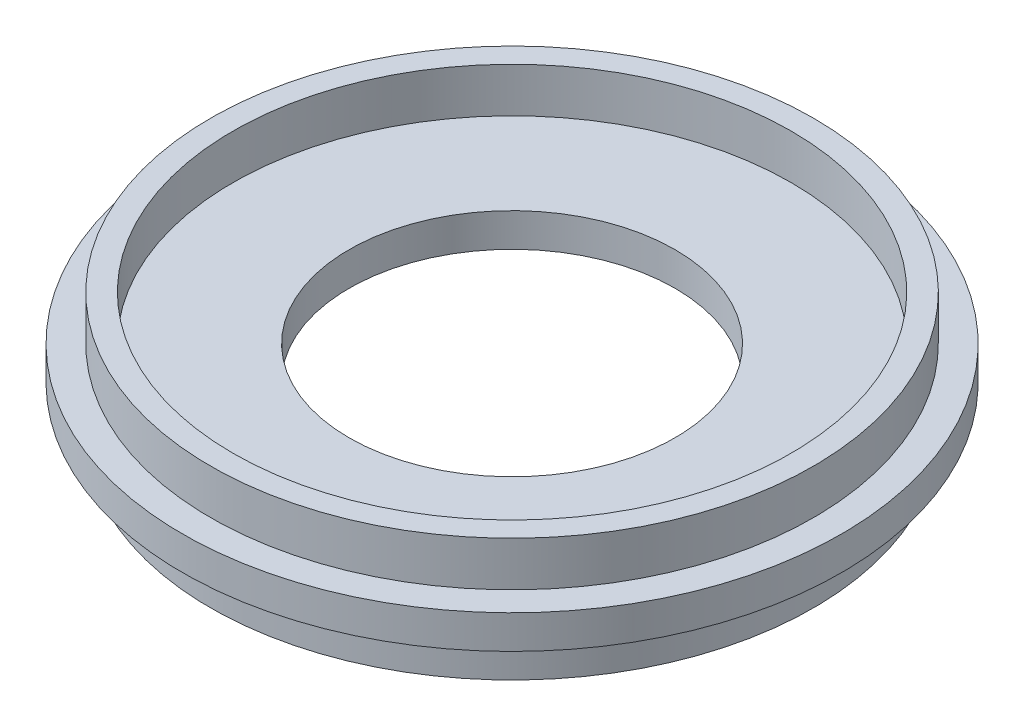
SolidWorks part; units mm, degrees
material "6061-T6 (SS)"
ref_plane "Front Plane" through (0, 0, 0) normal (0, 0, 1) x (1, 0, 0)
ref_plane "Top Plane" through (0, 0, 0) normal (0, 1, 0) x (1, 0, 0)
ref_plane "Right Plane" through (0, 0, 0) normal (1, 0, 0) x (0, 0, -1)
sketch "Sketch1" plane through (0, 0, 0) normal (0, 1, 0) x (1, 0, 0)
  line L5 (0, 0) -> (127.635, 0)
  line L6 (0, 0) -> (0, 127.635)
  line L7 (0, 127.635) -> (127.635, 127.635)
  line L8 (127.635, 0) -> (127.635, 127.635)
  dimension "D1" = 127.635
  dimension "D2" = 127.635
extrude "Boss-Extrude1" add sketch "Sketch1" along normal blind 9.525 contours L5 L8 L7 L6
sketch "Sketch12" plane through (0, 0, 0) normal (0, -1, 0) x (1, 0, 0)
  line L0 (63.8175, 0) -> (63.8175, -127.635) construction
  line L1 (0, 0) -> (127.635, 0) construction
  line L2 (0, -127.635) -> (127.635, -127.635) construction
  line L3 (0, -63.8175) -> (127.635, -63.8175) construction
  line L4 (0, 0) -> (0, -127.635) construction
  line L5 (127.635, 0) -> (127.635, -127.635) construction
  circle A0 centre (63.8175, -63.8175) radius 93.726
  dimension "D1" = 187.452
extrude "Boss-Extrude2" add sketch "Sketch12" against normal up to surface (9.525 mm away) contours A0 up to face at (63.8175, 9.525, -63.8175)
sketch "Sketch5" plane through (0, 9.525, 0) normal (0, 1, 0) x (1, 0, 0)
  circle A0 centre (63.8175, 63.8175) radius 46.355
  circle A3 centre (63.8175, 63.8175) radius 93.726 construction
  dimension "D1" = 92.71
extrude "Cut-Extrude1" cut sketch "Sketch5" against normal blind 9.525
sketch "Sketch11" plane through (0, 9.525, 0) normal (0, 1, 0) x (1, 0, 0)
  line L0 (63.8175, 63.8175) -> (63.8175, 115.443) construction
  circle A0 centre (63.8175, 115.443) radius 1.4351
  dimension "D2" = 2.8702
  dimension "D1" = 51.6255
extrude "Cut-Extrude3" [suppressed] cut sketch "Sketch11" against normal through all contours A0
pattern_circular "CirPattern1" [suppressed] count 12 over 360 of bodies 108
sketch "Sketch14" plane through (0, 9.525, 0) normal (0, -1, 0) x (1, 0, 0)
  line L0 (63.8175, -63.8175) -> (147.6375, -63.8175) construction
  line L1 (0, -19.2087) -> (0, 19.2087) construction
  line L2 (147.6375, -63.8175) -> (152.7175, -63.8175)
  line L3 (136.3808, -105.7742) -> (140.8401, -108.2104)
  circle A0 centre (63.8175, -63.8175) radius 46.355 construction
  arc A2 (147.6375, -63.8175) -> (136.3808, -105.7742) centre (63.8175, -63.8175) cw
  arc A3 (152.7175, -63.8175) -> (140.8401, -108.2104) centre (63.8175, -63.8175) cw
  point P0 (63.8175, -63.8175)
  dimension "D1" = 83.82
  dimension "D2" = 88.9
  dimension "D3" = 46.482
  dimension "D4" = 43.942
ref_plane "Support mirror reference plane" through (0, 4.7625, 0) normal (0, 1, 0) x (1, 0, 0)
sketch "Sketch25" plane through (0, 9.525, 0) normal (0, -1, 0) x (1, 0, 0)
  line L0 (63.8175, -63.8175) -> (123.0872, -4.5478) construction
  line L2 (123.0872, -4.5478) -> (126.6793, -0.9557)
  line L3 (144.7953, -42.1754) -> (149.6712, -40.7448)
  line L5 (63.8175, -63.8175) -> (147.6375, -63.8175) construction
  arc A2 (123.0872, -4.5478) -> (144.7953, -42.1754) centre (63.8175, -63.8175) cw
  arc A3 (126.6793, -0.9557) -> (149.6712, -40.7448) centre (63.8175, -63.8175) cw
  point P0 (63.8175, -63.8175)
  dimension "D1" = 83.82
  dimension "D2" = 88.9
  dimension "D3" = 46.482
  dimension "D4" = 43.942
  dimension "D5" = 45
sketch "Sketch30" plane through (0, 0, 0) normal (0, -1, 0) x (1, 0, 0)
  circle A0 centre (63.8175, -63.8175) radius 85.725
  circle A1 centre (63.8175, -63.8175) radius 79.375
  dimension "D1" = 171.45
  dimension "D2" = 158.75
extrude "Boss-Extrude3" add sketch "Sketch30" along normal blind 12.7
mirror "Mirror1" about plane through (0, 4.7625, 0) normal (0, 1, 0) of "Boss-Extrude3"
sketch "Sketch31" plane through (0, 0, 0) normal (0, -1, 0) x (-1, 0, 0)
  line L0 (-63.8175, -52.481) -> (-63.8175, 177.7216) construction
ref_plane "Plane1" through (0, 0, -149.5425) normal (0, 0, -1) x (-1, 0, 0)
ref_plane "Plane2" through (63.8175, 0, 0) normal (-1, 0, 0) x (0, 0, -1)
sketch "Sketch32" plane through (0, 0, -149.5425) normal (0, 0, -1) x (-1, 0, 0)
  line L4 (-63.8175, -87.3125) -> (-63.8175, 87.3125) construction
  line L5 (-149.5425, 0) -> (21.9075, 0) construction
  line L6 (21.9075, 9.525) -> (-149.5425, 9.525) construction
  circle A0 centre (-63.8175, -6.35) radius 1.4351
  circle A1 centre (-63.8175, 15.875) radius 1.4351
  dimension "D1" = 2.8702
  dimension "D2" = 2.8702
  dimension "D3" = 6.35
  dimension "D4" = 6.35
extrude "Cut-Extrude4" [suppressed] cut sketch "Sketch32" against normal blind 15.24
pattern_circular "CirPattern2" [suppressed] count 12 over 360 of bodies 125
